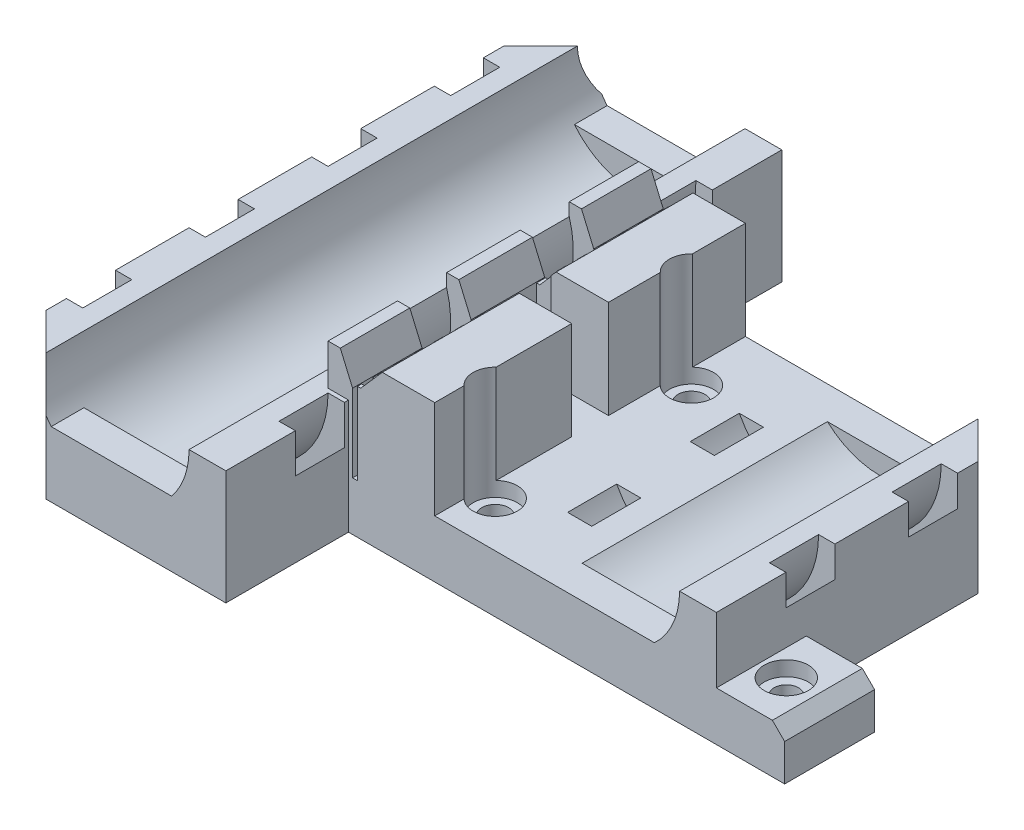
SolidWorks part; units mm, degrees
ref_plane "Front Plane" through (0, 0, 0) normal (0, 0, 1) x (1, 0, 0)
ref_plane "Top Plane" through (0, 0, 0) normal (0, 1, 0) x (1, 0, 0)
ref_plane "Right Plane" through (0, 0, 0) normal (1, 0, 0) x (0, 0, -1)
sketch "Sketch1" plane through (0, 0, 0) normal (0, 1, 0) x (1, 0, 0)
  line L0 (0.3879, -8.2154) -> (0.3879, 6.7846)
  line L1 (-27.6121, -8.2154) -> (0.3879, -8.2154)
  line L2 (-27.6121, -8.2154) -> (-27.6121, 59.7846)
  line L3 (-27.6121, 59.7846) -> (0.3879, 59.7846)
  line L4 (0.3879, 6.7846) -> (53.7379, 6.7846)
  line L5 (53.7379, 6.7846) -> (53.7379, 17.7846)
  line L6 (45.3879, 44.7846) -> (0.3879, 44.7846)
  line L7 (0.3879, 44.7846) -> (0.3879, 59.7846)
  line L8 (53.7379, 17.7846) -> (45.3879, 17.7846)
  line L9 (45.3879, 44.7846) -> (45.3879, 17.7846)
  circle A0 centre (12.7879, 36.3346) radius 1.65
  circle A1 centre (12.7879, 12.3346) radius 1.65
  circle A2 centre (48.5879, 12.1346) radius 1.5
  dimension "D10" = 3.3
  dimension "D13" = 3.3
  dimension "D15" = 3
  dimension "D1" = 68
  dimension "D2" = 28
  dimension "D3" = 15
  dimension "D4" = 15
  dimension "D5" = 53.35
  dimension "D6" = 28
  dimension "D7" = 45
  dimension "D8" = 11
  dimension "D9" = 24
  dimension "D11" = 40.4
  dimension "D12" = 40.4
  dimension "D14" = 8.45
  dimension "D16" = 32.65
  dimension "D17" = 5.15
extrude "Boss-Extrude1" add sketch "Sketch1" along normal blind 19
sketch "Sketch2" plane through (0, 19, 0) normal (0, 1, 0) x (1, 0, 0)
  line L1 (-27.6121, 59.7846) -> (0.3879, 59.7846)
  line L2 (-27.6121, 59.7846) -> (-27.6121, -8.2154)
  line L3 (-27.6121, -8.2154) -> (0.3879, -8.2154)
  line L4 (0.3879, 59.7846) -> (0.3879, -8.2154)
extrude "Cut-Extrude1" cut sketch "Sketch2" against normal blind 5
sketch "Sketch3" plane through (0, 0, 8.2154) normal (0, 0, 1) x (1, 0, 0)
  line L1 (-27.6121, 14) -> (0.3879, 14) construction
  line L2 (0.3879, 14) -> (0.3879, 0) construction
  circle A0 centre (-13.6121, 14) radius 9.5
  dimension "D2" = 19
  dimension "D1" = 0
  dimension "D3" = 14
extrude "Cut-Extrude2" cut sketch "Sketch3" against normal blind 79.7876
sketch "Sketch4" plane through (0, 0, 0) normal (0, -1, 0) x (1, 0, 0)
  line L0 (0.3879, 8.2154) -> (0.3879, -6.7846) construction
  line L1 (-27.6121, 8.2154) -> (0.3879, 8.2154)
  line L2 (-27.6121, 8.2154) -> (-27.6121, 4.2154)
  line L3 (-27.6121, 4.2154) -> (0.3879, 4.2154)
  line L4 (0.3879, 8.2154) -> (0.3879, 4.2154)
  line L5 (0.3879, -44.7846) -> (0.3879, -59.7846) construction
  line L6 (-27.6121, -59.7846) -> (0.3879, -59.7846)
  line L7 (-27.6121, -59.7846) -> (-27.6121, -55.7846)
  line L8 (-27.6121, -55.7846) -> (0.3879, -55.7846)
  line L9 (0.3879, -59.7846) -> (0.3879, -55.7846)
  dimension "D1" = 4
  dimension "D2" = 4
extrude "Boss-Extrude3" add sketch "Sketch4" against normal blind 8
sketch "Sketch5" plane through (0, 14, 0) normal (0, 1, 0) x (1, 0, 0)
  line L0 (-23.1121, 59.7846) -> (-23.1121, -8.2154) construction
  line L1 (-25.6121, 0.2846) -> (-28.4121, 0.2846)
  line L2 (-25.6121, 0.2846) -> (-25.6121, 6.2846)
  line L3 (-25.6121, 6.2846) -> (-28.4121, 6.2846)
  line L4 (-28.4121, 0.2846) -> (-28.4121, 6.2846)
  line L5 (-20.9776, -4.2154) -> (-6.2466, -4.2154) construction
  dimension "D1" = 6
  dimension "D2" = 2.8
  dimension "D3" = 2.5
  dimension "D4" = 4.5
ref_axis "Axis1" through (-13.6121, 14, -59.7846) along (0, 0, 1)
revolve "Cut-Revolve2" cut sketch "Sketch5" angle 360 about axis through (-13.6121, 14, -59.7846) along (0, 0, 1)
sketch "Sketch7" plane through (0, 14, 0) normal (0, 1, 0) x (1, 0, 0)
  line L0 (0.3879, 44.7846) -> (0.3879, 6.7846)
  line L1 (0.3879, 44.7846) -> (-2.1121, 44.7846)
  line L2 (0.3879, 6.7846) -> (-2.1121, 6.7846)
  line L3 (-2.1121, 44.7846) -> (-2.1121, 6.7846)
  dimension "D1" = 2.5
extrude "Boss-Extrude4" add sketch "Sketch7" along normal blind 5
sketch "Sketch8" plane through (0, 19, 0) normal (0, 1, 0) x (1, 0, 0)
  line L0 (-2.1121, 6.7846) -> (53.7379, 6.7846) construction
  line L1 (0.8879, 6.7846) -> (1.4879, 6.7846)
  line L2 (0.8879, 6.7846) -> (0.8879, 44.7846)
  line L3 (0.8879, 44.7846) -> (1.4879, 44.7846)
  line L4 (1.4879, 6.7846) -> (1.4879, 44.7846)
  line L5 (45.3879, 44.7846) -> (-2.1121, 44.7846) construction
  line L6 (0.3879, 44.7846) -> (0.3879, 59.7846) construction
  dimension "D1" = 0.5
  dimension "D2" = 0.6
extrude "Cut-Extrude3" cut sketch "Sketch8" against normal blind 13
pattern_linear "LPattern1" count 4 spacing 15 along (0, 0, -1) of "Cut-Revolve2"
sketch "Sketch9" plane through (0, 0, -6.7846) normal (0, 0, 1) x (1, 0, 0)
  line L0 (0.8879, 19) -> (-0.6121, 19)
  line L1 (0.8879, 6) -> (0.8879, 19) construction
  line L2 (-2.1121, 19) -> (0.8879, 19) construction
  line L3 (-0.6121, 19) -> (0.8879, 15.5)
  line L4 (0.8879, 15.5) -> (0.8879, 19)
extrude "Cut-Extrude4" cut sketch "Sketch9" against normal blind 54
sketch "Sketch11" plane through (0, 0, -6.7846) normal (0, 0, 1) x (1, 0, 0)
  line L0 (0.3879, 0) -> (53.7379, 0) construction
  circle A0 centre (31.3879, 14) radius 9.5
  dimension "D1" = 19
  dimension "D2" = 45
  dimension "D3" = 14
extrude "Cut-Extrude6" cut sketch "Sketch11" along direction (0, 0, -1) on the side against the normal offset from surface (75 mm away) 75 up to face at (9.8333, 11.9545, -6.7846)
ref_axis "Axis2" through (31.3879, 14, -44.7846) along (0, 0, 1)
sketch "Sketch12" plane through (0, 19, 0) normal (0, 1, 0) x (1, 0, 0)
  line L0 (23.3101, 44.7846) -> (1.4879, 44.7846) construction
  line L1 (10.9379, 44.7846) -> (31.3879, 44.7846)
  line L2 (10.9379, 44.7846) -> (10.9379, 6.7846)
  line L3 (10.9379, 6.7846) -> (31.3879, 6.7846)
  line L4 (31.3879, 44.7846) -> (31.3879, 6.7846)
  line L5 (31.3879, 44.7846) -> (31.3879, 6.7846) construction
  line L6 (1.4879, 6.7846) -> (1.4879, 44.7846) construction
  dimension "D1" = 0
  dimension "D2" = 9.45
extrude "Cut-Extrude7" cut sketch "Sketch12" against normal blind 12
sketch "Sketch14" plane through (0, 19, 0) normal (0, 1, 0) x (1, 0, 0)
  line L1 (39.4656, 44.7846) -> (53.7379, 44.7846)
  line L2 (39.4656, 44.7846) -> (39.4656, 6.7846)
  line L3 (39.4656, 6.7846) -> (53.7379, 6.7846)
  line L4 (53.7379, 44.7846) -> (53.7379, 6.7846)
extrude "Cut-Extrude9" cut sketch "Sketch14" against normal blind 5
sketch "Sketch15" plane through (0, 14, 0) normal (0, 1, 0) x (1, 0, 0)
  line L0 (40.8879, 6.7846) -> (53.7379, 6.7846) construction
  line L1 (53.7379, 17.7846) -> (45.3879, 17.7846)
  line L2 (53.7379, 17.7846) -> (53.7379, 6.7846)
  line L3 (53.7379, 6.7846) -> (45.3879, 6.7846)
  line L4 (45.3879, 17.7846) -> (45.3879, 6.7846)
extrude "Cut-Extrude10" cut sketch "Sketch15" against normal blind 8
sketch "Sketch16" plane through (0, 0, 0) normal (0, -1, 0) x (-1, 0, 0)
  line L0 (-0.3879, 6.7846) -> (-53.7379, 6.7846) construction
  line L1 (-44.6036, 6.7846) -> (-16.2094, 6.7846)
  line L2 (-44.6036, 6.7846) -> (-44.6036, 10.7846)
  line L3 (-44.6036, 10.7846) -> (-16.2094, 10.7846)
  line L4 (-16.2094, 6.7846) -> (-16.2094, 10.7846)
  line L6 (-45.3879, 44.7846) -> (-21.7206, 44.7846)
  line L7 (-45.3879, 44.7846) -> (-45.3879, 40.7846)
  line L8 (-45.3879, 40.7846) -> (-21.7206, 40.7846)
  line L9 (-21.7206, 44.7846) -> (-21.7206, 40.7846)
  dimension "D1" = 4
  dimension "D2" = 4
extrude "Boss-Extrude5" add sketch "Sketch16" against normal blind 7
sketch "Sketch17" plane through (0, 14, 0) normal (0, 1, 0) x (1, 0, 0)
  line L0 (40.8879, 44.7846) -> (40.8879, 6.7846) construction
  line L1 (43.3879, 21.2846) -> (45.8879, 21.2846)
  line L2 (43.3879, 21.2846) -> (43.3879, 15.2846)
  line L3 (43.3879, 15.2846) -> (45.8879, 15.2846)
  line L4 (45.8879, 21.2846) -> (45.8879, 15.2846)
  line L5 (24.9653, 10.7846) -> (37.8105, 10.7846) construction
  dimension "D1" = 2.5
  dimension "D2" = 6
  dimension "D3" = 2.5
  dimension "D4" = 4.5
revolve "Cut-Revolve3" cut sketch "Sketch17" angle 360 about axis through (31.3879, 14, -44.7846) along (0, 0, 1)
pattern_linear "LPattern2" count 2 spacing 15 along (0, 0, -1) of "Cut-Revolve3"
sketch "Sketch18" plane through (0, 6, 0) normal (0, 1, 0) x (1, 0, 0)
  circle A0 centre (48.5879, 12.1346) radius 2.7
  dimension "D1" = 5.4
extrude "Cut-Extrude11" cut sketch "Sketch18" against normal blind 1.8
sketch "Sketch19" plane through (0, 7, 0) normal (0, 1, 0) x (1, 0, 0)
  circle A0 centre (12.7879, 36.3346) radius 2.7
  circle A1 centre (12.7879, 12.3346) radius 2.7
  dimension "D1" = 5.4
  dimension "D2" = 5.4
extrude "Cut-Extrude12" cut sketch "Sketch19" against normal blind 13.8 from offset 12
sketch "Sketch20" plane through (0, 19, 0) normal (0, 1, 0) x (1, 0, 0)
  line L0 (1.4879, 6.7846) -> (1.4879, 44.7846) construction
  line L1 (3.8879, 42.2846) -> (1.4879, 42.2846)
  line L2 (3.8879, 42.2846) -> (3.8879, 43.6846)
  line L3 (3.8879, 43.6846) -> (1.4879, 43.6846)
  line L4 (1.4879, 42.2846) -> (1.4879, 43.6846)
  line L5 (10.9379, 44.7846) -> (1.4879, 44.7846) construction
  dimension "D1" = 1.4
  dimension "D2" = 2.4
  dimension "D3" = 1.1
extrude "Cut-Extrude13" cut sketch "Sketch20" against normal up to surface (13 mm away) up to face at (1.1879, 6, -25.7846)
pattern_linear "LPattern3" count 15 spacing 2.5 along (0, 0, 1) of "Cut-Extrude13"
sketch "Sketch21" plane through (0, 0, -6.7846) normal (0, 0, 1) x (1, 0, 0)
  line L0 (1.4879, 19) -> (1.4879, 16)
  line L1 (1.4879, 6) -> (1.4879, 19) construction
  line L2 (1.4879, 16) -> (1.8879, 16)
  line L3 (1.8879, 16) -> (4.5271, 19)
  line L4 (1.4879, 19) -> (10.9379, 19) construction
  line L5 (4.5271, 19) -> (1.4879, 19)
  dimension "D1" = 3
  dimension "D2" = 0.4
extrude "Cut-Extrude14" cut sketch "Sketch21" against normal blind 39.8
sketch "Sketch23" plane through (0, 0, -6.7846) normal (0, 0, 1) x (1, 0, 0)
  line L1 (10.9379, 19) -> (1.2977, 19)
  line L2 (10.9379, 19) -> (10.9379, 7)
  line L3 (10.9379, 7) -> (1.2977, 7)
  line L4 (1.2977, 19) -> (1.2977, 7)
extrude "Cut-Extrude15" cut sketch "Sketch23" against normal mid plane 4.5 from offset 19 offset against normal yes
chamfer "Chamfer2" distance 1.5 angle 45 1 edges at (53.7379, 6, -12.2846)
chamfer "Chamfer3" distance 6 angle 45 3 edges at (45.3879, 7, -44.7846) (-27.6121, 7, -59.7846) (-27.6121, 7, 8.2154)
